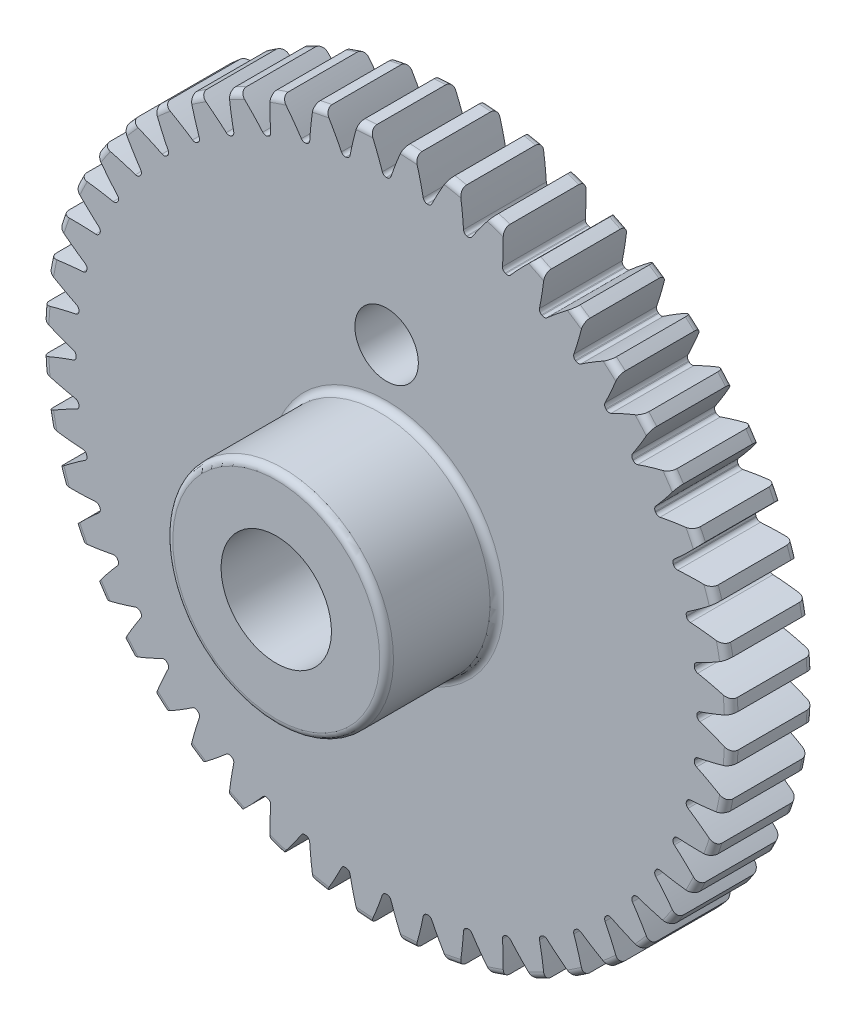
SolidWorks part; units mm, degrees
material "Delrin 2700 NC010, Low Viscosity Acetal Copolymer (SS)"
ref_plane "Front Plane" through (0, 0, 0) normal (0, 0, 1) x (1, 0, 0)
ref_plane "Top Plane" through (0, 0, 0) normal (0, 1, 0) x (1, 0, 0)
ref_plane "Right Plane" through (0, 0, 0) normal (1, 0, 0) x (0, 0, -1)
sketch "Sketch1" plane through (0, 0, 0) normal (0, 0, 1) x (1, 0, 0)
  line L0 (-609.6, 0) -> (609.6, 0) construction
  circle A0 centre (0, 0) radius 25 construction
  circle A1 centre (0, 0) radius 24 construction
  circle A2 centre (0, 0) radius 22.5 construction
  circle A3 centre (0, 0) radius 8 construction
  circle A4 centre (0, 0) radius 4 construction
  dimension "D2" = 1
  dimension "D3" = 2.5
  dimension "D1" = 2.5
sketch "Sketch2" plane through (0, 0, 0) normal (1, 0, 0) x (0, 0, -1)
  line L0 (0, 0) -> (-6, 0) construction
  line L1 (-6, 0) -> (-14, 0) construction
  dimension "Overall Width" = 14
  dimension "Face Width" = 6
sketch "Sketch4" plane through (0, 0, 0) normal (1, 0, 0) x (0, 0, -1)
  line L0 (-14, 4) -> (-14, 8)
  line L1 (-14, 8) -> (-6, 8)
  line L2 (-6, 8) -> (-6, 25)
  line L3 (-6, 25) -> (0, 25)
  line L4 (0, 25) -> (0, 4)
  line L5 (-6, 8) -> (-6, 0) construction
  line L6 (0, 25) -> (0, -25) construction
  line L7 (-6, 8) -> (0, 8) construction
  line L12 (-14, 4) -> (0, 4)
revolve "Revolve1" add sketch "Sketch4" angle 360 about L1
fillet "Fillet2" radius 0.5 4 edges at (0, 8, 14) (0, 8, 6) (0, 25, 6) (0, 25, 0)
sketch "Sketch7" plane through (0, 0, 6) normal (0, 0, 1) x (1, 0, 0)
  line L0 (0, 0) -> (0, 25) construction
  line L1 (0.7853, 23.9872) -> (1.1807, 24.9721) construction
  line L3 (1.6351, 24.9465) -> (1.5697, 23.9486) construction
  line L4 (1.5697, 23.9486) -> (1.4716, 22.4518) construction
  line L5 (0, 0) -> (1.4716, 22.4518) construction
  line L6 (0.7853, 23.9872) -> (0, 0) construction
  line L7 (0.7853, 23.9872) -> (0.818, 24.9866) construction
  line L8 (0.7853, 23.9872) -> (0, 0) construction
  circle A0 centre (0, 0) radius 25 construction
  arc A1 (-0.0275, 22.5) -> (0.0275, 22.5) centre (0, 0) cw
  circle A2 centre (0, 0) radius 22.5 construction
  arc A3 (-0.7853, 23.9872) -> (0.7853, 23.9872) centre (0, 0) cw construction
  circle A4 centre (0, 0) radius 24 construction
  arc A5 (2.0637, 24.9147) -> (1.2059, 24.9709) centre (0, 0) ccw construction
  arc A6 (0.7853, 23.9872) -> (2.3524, 23.8844) centre (0, 0) cw construction
  arc A7 (-1.2059, 24.9709) -> (1.2059, 24.9709) centre (0, 0) cw
  arc A8 (0.3122, 22.7043) -> (1.2059, 24.9709) centre (23.0572, 15.0452) cw
  arc A9 (-0.3122, 22.7043) -> (-1.2059, 24.9709) centre (-23.0572, 15.0452) ccw
  arc A10 (-0.0275, 22.5) -> (-0.3122, 22.7043) centre (-0.0278, 22.8) cw
  arc A11 (0.0275, 22.5) -> (0.3122, 22.7043) centre (0.0278, 22.8) ccw
  point P26 (-0.244, 22.4987)
  point P29 (0.244, 22.4987)
  dimension "D4" = 0.3
  dimension "D5" = 24
  dimension "D3" = 20
  dimension "D1" = 3.1416
  dimension "D2" = 1.5708
extrude "Cut-Extrude2" cut sketch "Sketch7" against normal through all
pattern_circular "CirPattern1" count 48 over 360 about axis through (0, 0, 14) along (0, 0, -1) of "Cut-Extrude2"
ref_axis "Axis1" through (0, 0, 14) along (0, 0, -1)
sketch "Sketch8" plane through (0, 0, 0) normal (0, 0, -1) x (-1, 0, 0)
  circle A0 centre (0, 12) radius 2.3
  circle A1 centre (0, 0) radius 4 construction
  dimension "D1" = 4.6
  dimension "D2" = 12
extrude "Cut-Extrude3" cut sketch "Sketch8" against normal through all
equation "\"D1@Sketch1\"=2.5*(\"Pitch Dia.@Sketch1\"/\"Number of Teeth@Sketch1\")"
equation "\"D1@CirPattern1\"=\"Number of Teeth@Sketch1\""
equation "\"D1@Fillet2\"=\"OD@Sketch1\"*.01"
equation "\"D1@Sketch7\"=3.14159*(\"Pitch Dia.@Sketch1\"/\"Number of Teeth@Sketch1\")"
equation "\"D2@Sketch7\"=\"D1@Sketch7\"/2"
equation "\"D4@Sketch7\"=\"D1@Sketch7\"*.0955"
equation "\"D5@Sketch7\"=\"Pitch Dia.@Sketch1\"/2"
